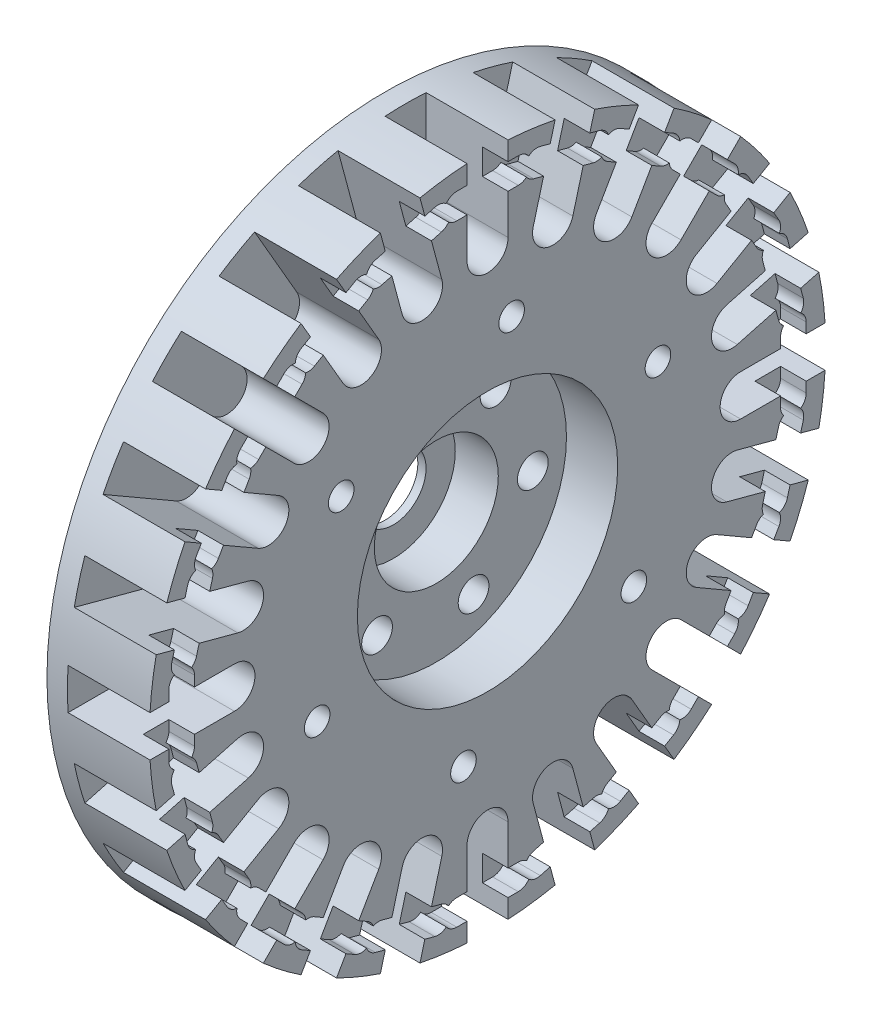
SolidWorks part; units mm, degrees
material "1060 Alloy"
ref_plane "Front Plane" through (0, 0, 0) normal (0, 0, 1) x (1, 0, 0)
ref_plane "Top Plane" through (0, 0, 0) normal (0, 1, 0) x (1, 0, 0)
ref_plane "Right Plane" through (0, 0, 0) normal (1, 0, 0) x (0, 0, -1)
sketch "Sketch1" plane through (0, 0, 0) normal (1, 0, 0) x (0, 0, -1)
  circle A0 centre (0, 0) radius 33
  circle A1 centre (0, 0) radius 3.2
  dimension "D1" = 66
  dimension "D2" = 6.4
extrude "Boss-Extrude1" add sketch "Sketch1" along normal blind 10
sketch "Sketch2" plane through (10, 0, 0) normal (1, 0, 0) x (0, 0, -1)
  line L0 (-2, 33) -> (2, 33)
  line L1 (2, 33) -> (2, 24.7)
  line L2 (-2, 24.7) -> (-2, 33)
  arc A0 (2, 24.7) -> (-2, 24.7) centre (0, 24.7) cw
  circle A1 centre (0, 0) radius 33 construction
  dimension "D1" = 4
  dimension "D2" = 8.3
extrude "Cut-Extrude1" cut sketch "Sketch2" against normal blind 8
sketch "Sketch3" plane through (10, 0, 0) normal (1, 0, 0) x (0, 0, -1)
  line L0 (-3, 29.85) -> (3, 29.85) construction
  line L1 (-3, 31.1) -> (3, 31.1)
  line L2 (-3, 28.6) -> (3, 28.6)
  arc A0 (-3, 31.1) -> (-3, 28.6) centre (-3, 29.85) ccw
  arc A1 (3, 28.6) -> (3, 31.1) centre (3, 29.85) ccw
  arc A2 (-2, 24.7) -> (2, 24.7) centre (0, 24.7) ccw construction
  point P2 (0, 29.85)
  dimension "D1" = 1.25
  dimension "D2" = 5.15
  dimension "D3" = 6
extrude "Cut-Extrude2" cut sketch "Sketch3" against normal blind 2.5
pattern_circular "CirPattern1" count 24 over 360 about axis through (10, 0, 0) along (1, 0, 0) of "Cut-Extrude1", "Cut-Extrude2"
hole_wizard "Tap Drill for M3x0.5 Tap1" positions "Sketch6" profile "Sketch5" hole size "M3x0.5" standard "ANSI Metric"
sketch "Sketch6" plane through (10, 0, 0) normal (1, 0, 0) x (0, 0, -1)
  line L0 (2.3495, 17.846) -> (0, 0) construction
  line L1 (0, 0) -> (3.2, 0) construction
  circle A2 centre (0, 0) radius 3.2 construction
  point P0 (2.3495, 17.846)
  dimension "D1" = 82.5
  dimension "D2" = 18
sketch "Sketch5" plane through (10, 17.846, -2.3495) normal (0, 1, 0) x (0, 0, -1)
  line L0 (0, 0) -> (0, 8.7511)
  line L1 (0, 8.7511) -> (1.25, 8)
  line L2 (1.25, 8) -> (1.25, 0)
  line L5 (1.25, 0) -> (0, 0)
  line L10 (0, 8.7511) -> (-1.25, 8) construction
  line L11 (0, -6.35) -> (0, 107.95) construction
  dimension "Hole Dia." = 2.5
  dimension "Hole Depth" = 8
  dimension "Drill Angle" = 118
pattern_circular "CirPattern2" count 6 over 360 about axis through (10, 0, 0) along (1, 0, 0) of "Tap Drill for M3x0.5 Tap1"
sketch "Sketch7" plane through (10, 0, 0) normal (-1, 0, 0) x (0, 0, 1)
  circle A0 centre (0, 0) radius 12.705
  dimension "D1" = 25.41
extrude "Cut-Extrude3" cut sketch "Sketch7" along normal blind 5
sketch "Sketch12" plane through (5, 0, 0) normal (1, 0, 0) x (0, 0, -1)
  circle A0 centre (0, 0) radius 6.05
  dimension "D1" = 12.1
extrude "Cut-Extrude5" cut sketch "Sketch12" against normal blind 4.2
sketch "Sketch11" plane through (10, 0, 0) normal (1, 0, 0) x (0, 0, -1)
  line L0 (0, 0) -> (-10.5081, 0) construction
  line L1 (-3.6355, 8.7769) -> (0, 0) construction
  circle A0 centre (-3.6355, 8.7769) radius 1.5
  dimension "D1" = 3
  dimension "D2" = 9.5
  dimension "D3" = 67.5
extrude "Cut-Extrude4" cut sketch "Sketch11" against normal up to next
chamfer "Chamfer1" distance 1.5 angle 45 1 edges at (0, 8.7769, 2.1355)
pattern_circular "CirPattern3" count 6 over 360 about axis through (0, 0, 0) along (1, 0, 0) of "Cut-Extrude4", "Chamfer1"
